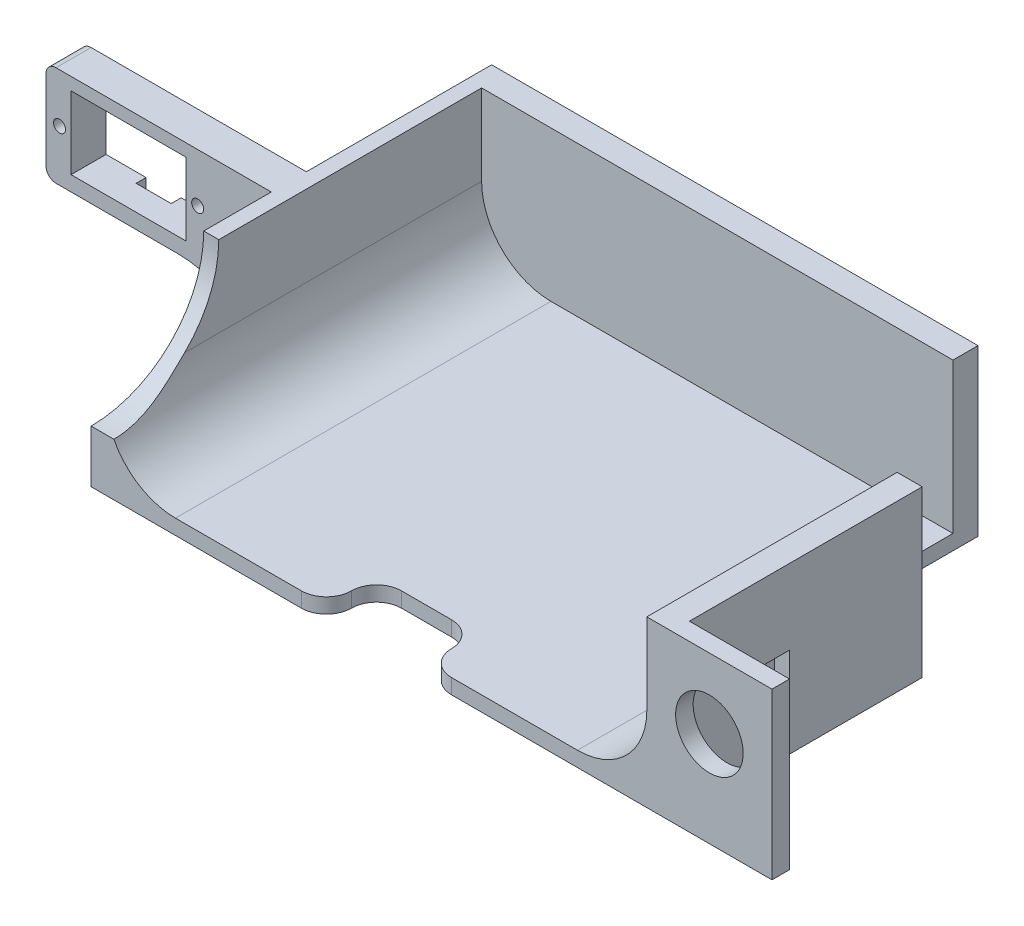
SolidWorks part; units mm, degrees
ref_plane "Plan de face" through (0, 0, 0) normal (0, 0, 1) x (1, 0, 0)
ref_plane "Plan de dessus" through (0, 0, 0) normal (0, 1, 0) x (1, 0, 0)
ref_plane "Plan de droite" through (0, 0, 0) normal (1, 0, 0) x (0, 0, -1)
sketch "Esquisse1" plane through (0, 0, 0) normal (0, 1, 0) x (1, 0, 0)
  line L1 (0, 0) -> (138, 0)
  line L2 (0, 0) -> (0, 75)
  line L3 (0, 75) -> (138, 75)
  line L4 (138, 0) -> (138, 75)
  dimension "D1" = 138
  dimension "D2" = 75
extrude "Boss.-Extru.1" add sketch "Esquisse1" along normal blind 3
sketch "Esquisse2" plane through (0, 3, 0) normal (0, 1, 0) x (1, 0, 0)
  line L0 (0, 0) -> (138, 0) construction
  line L1 (0, 75) -> (5, 75)
  line L2 (0, 75) -> (0, 0)
  line L3 (0, 0) -> (5, 0)
  line L4 (5, 75) -> (5, 0)
  line L6 (138, 75) -> (113, 75)
  line L7 (138, 75) -> (138, 0)
  line L8 (138, 0) -> (113, 0)
  line L9 (113, 75) -> (113, 0)
  dimension "D1" = 25
  dimension "D2" = 5
extrude "Boss.-Extru.2" add sketch "Esquisse2" along normal blind 30
fillet "Congé1" radius 13.85 2 edges at (113, 3, -37.5) (5, 3, -37.5)
sketch "Esquisse3" plane through (0, 0, -75) normal (0, 0, -1) x (-1, 0, 0)
  line L1 (-138, 0) -> (0, 0)
  line L2 (-138, 0) -> (-138, 33)
  line L3 (-138, 33) -> (0, 33)
  line L4 (0, 0) -> (0, 33)
extrude "Boss.-Extru.3" add sketch "Esquisse3" along normal blind 5
sketch "Esquisse4" plane through (0, 0, 0) normal (-1, 0, 0) x (0, 0, 1)
  line L1 (0, 33) -> (-25, 33)
  line L2 (0, 33) -> (0, 13)
  line L3 (0, 13) -> (-25, 13)
  line L4 (-25, 33) -> (-25, 13)
  dimension "D1" = 25
  dimension "D2" = 20
extrude "Enlèv. mat.-Extru.1" [suppressed] cut sketch "Esquisse4" against normal blind 6
sketch "Esquisse5" plane through (0, 33, 0) normal (0, 1, 0) x (1, 0, 0)
  line L0 (113, 75) -> (113, 0) construction
  line L1 (138, 80) -> (118, 80)
  line L2 (138, 80) -> (138, 3.5)
  line L3 (138, 3.5) -> (118, 3.5)
  line L4 (118, 80) -> (118, 3.5)
  line L5 (113, 0) -> (138, 0) construction
  dimension "D1" = 5
  dimension "D2" = 3.5
extrude "Enlèv. mat.-Extru.2" cut sketch "Esquisse5" against normal blind 30
sketch "Esquisse6" plane through (0, 0, 0) normal (0, 0, 1) x (1, 0, 0)
  line L0 (113, 33) -> (138, 33) construction
  line L3 (138, 33) -> (138, 0) construction
  circle A0 centre (125.5, 19) radius 6.25
  dimension "D3" = 12.5
  dimension "D1" = 14
  dimension "D2" = 12.5
extrude "Enlèv. mat.-Extru.3" cut sketch "Esquisse6" against normal up to surface (3.5 mm away) up to face at (128, 18, -3.5)
sketch "Esquisse7" plane through (0, 0, -80) normal (0, 0, -1) x (-1, 0, 0)
  line L1 (-138, 0) -> (-118, 0)
  line L2 (-138, 0) -> (-138, 3)
  line L3 (-138, 3) -> (-118, 3)
  line L4 (-118, 0) -> (-118, 3)
extrude "Enlèv. mat.-Extru.4" cut sketch "Esquisse7" against normal blind 30
sketch "Esquisse8" plane through (0, 33, 0) normal (0, 1, 0) x (1, 0, 0)
  line L0 (99.15, 0) -> (99.15, 75) construction
  line L1 (118, 80) -> (99.15, 80)
  line L2 (118, 80) -> (118, 50)
  line L3 (118, 50) -> (99.15, 50)
  line L4 (99.15, 80) -> (99.15, 50)
  dimension "D1" = 30
extrude "Enlèv. mat.-Extru.5" cut sketch "Esquisse8" against normal up to surface (33 mm away) up to face at (85.3333, 0, -43.3333)
sketch "Esquisse10" plane through (118, 0, 0) normal (1, 0, 0) x (0, 0, -1)
  line L0 (50, 3) -> (3.5, 3) construction
  line L1 (15.5, 3) -> (23.5, 3)
  line L2 (15.5, 3) -> (15.5, 18)
  line L3 (15.5, 18) -> (23.5, 18)
  line L4 (23.5, 3) -> (23.5, 18)
  dimension "D1" = 12
  dimension "D2" = 8
  dimension "D3" = 15
extrude "Enlèv. mat.-Extru.6" cut sketch "Esquisse10" against normal offset from surface (3 mm away) 2 up to face at (113, 24.925, -25)
sketch "Esquisse11" plane through (0, 3, 0) normal (0, 1, 0) x (1, 0, 0)
  line L1 (115, 23.5) -> (118, 23.5)
  line L2 (115, 23.5) -> (115, 15.5)
  line L3 (115, 15.5) -> (131, 15.5)
  line L8 (138, 3.5) -> (131, 3.5)
  line L9 (131, 15.5) -> (131, 3.5)
  line L10 (138, 50) -> (138, 3.5)
  line L11 (118, 50) -> (138, 50)
  line L12 (118, 50) -> (118, 23.5)
  dimension "D1" = 12
  dimension "D2" = 7
  dimension "D3" = 20
extrude "Enlèv. mat.-Extru.7" cut sketch "Esquisse11" against normal up to surface (3 mm away) up to face at (79.05, 0, -43.3333)
sketch "Esquisse12" plane through (0, 0, 0) normal (-1, 0, 0) x (0, 0, 1)
  line L1 (-80, 33) -> (0, 33)
  line L2 (-80, 33) -> (-80, 0)
  line L3 (-80, 0) -> (0, 0)
  line L4 (0, 33) -> (0, 0)
extrude "Enlèv. mat.-Extru.8" cut sketch "Esquisse12" against normal blind 2
sketch "Esquisse13" plane through (0, 0, 0) normal (0, 0, 1) x (1, 0, 0)
  line L0 (37, 0) -> (44.5969, -20)
  line L1 (2, 0) -> (138, 0) construction
  line L2 (44.5969, -20) -> (71.5969, -20)
  line L3 (71.5969, -20) -> (78, 0)
  line L4 (78, 0) -> (37, 0)
  line L7 (113, 33) -> (113, 16.85) construction
  dimension "D1" = 35
  dimension "D2" = 27
  dimension "D3" = 35
  dimension "D4" = 20
  dimension "D5" = 21
extrude "Boss.-Extru.4" [suppressed] add sketch "Esquisse13" against normal blind 7
sketch "Esquisse14" [suppressed] plane through (0, 0, 0) normal (0, 0, 1) x (1, 0, 0)
  line L0 (44.5969, -20) -> (71.5969, -20) construction
  line L1 (46.5, -2.5) -> (69.5, -2.5)
  line L2 (46.5, -2.5) -> (46.5, -17)
  line L3 (46.5, -17) -> (69.5, -17)
  line L4 (69.5, -2.5) -> (69.5, -17)
  dimension "D1" = 23
  dimension "D2" = 9.5
  dimension "D3" = 3
  dimension "D4" = 14.5
extrude "Enlèv. mat.-Extru.9" [suppressed] cut sketch "Esquisse14" against normal up to surface (7 mm away) up to face at (131.75, 19, 0)
fillet "Congé2" [suppressed] radius 10
sketch "Esquisse15" plane through (2, 0, 0) normal (-1, 0, 0) x (0, 0, 1)
  line L0 (0, 33) -> (-80, 33) construction
  line L1 (-42.9875, 33) -> (-35.9875, 33)
  line L2 (-42.9875, 33) -> (-42.9875, 13)
  line L3 (-42.9875, 13) -> (-35.9875, 13)
  line L4 (-35.9875, 33) -> (-35.9875, 13)
  dimension "D1" = 20
  dimension "D2" = 7
extrude "Boss.-Extru.5" add sketch "Esquisse15" along normal blind 45
sketch "Esquisse16" plane through (0, 0, -35.9875) normal (0, 0, 1) x (1, 0, 0)
  line L0 (-20.5, 33) -> (-20.5, 13) construction
  line L1 (-43, 33) -> (2, 33) construction
  line L2 (-43, 13) -> (2, 13) construction
  line L3 (-43, 23) -> (2, 23) construction
  line L4 (-43, 13) -> (-43, 33) construction
  line L5 (2, 13) -> (2, 33) construction
  line L7 (-38, 30.5) -> (-15, 30.5)
  line L8 (-38, 30.5) -> (-38, 16)
  line L9 (-38, 16) -> (-15, 16)
  line L10 (-15, 30.5) -> (-15, 16)
  dimension "D1" = 23
  dimension "D2" = 14.5
  dimension "D3" = 2.5
  dimension "D4" = 5
extrude "Enlèv. mat.-Extru.10" cut sketch "Esquisse16" against normal up to surface (7 mm away) up to face at (-20.5, 23, -42.9875)
fillet "Congé3" radius 20 1 edges at (2, 13, -39.4875)
fillet "Congé4" radius 2 2 edges at (-43, 33, -39.4875) (-43, 13, -39.4875)
sketch "Esquisse18" plane through (0, 0, -42.9875) normal (0, 0, -1) x (-1, 0, 0)
  line L0 (15, 16) -> (38, 16) construction
  line L1 (23, 16) -> (30, 16)
  line L2 (23, 16) -> (23, 13)
  line L3 (23, 13) -> (30, 13)
  line L4 (30, 16) -> (30, 13)
  line L6 (41, 13) -> (16.735, 13) construction
  dimension "D1" = 8
  dimension "D2" = 8
extrude "Enlèv. mat.-Extru.11" cut sketch "Esquisse18" against normal blind 2
sketch "Esquisse20" plane through (0, 0, -42.9875) normal (0, 0, -1) x (-1, 0, 0)
  line L0 (38, 30.5) -> (15, 30.5) construction
  line L1 (10.4, 25.9) -> (15, 25.9)
  line L2 (10.4, 25.9) -> (10.4, 20.6)
  line L3 (10.4, 20.6) -> (15, 20.6)
  line L4 (15, 25.9) -> (15, 20.6)
  line L5 (38, 25.9) -> (42.6, 25.9)
  line L6 (38, 25.9) -> (38, 20.6)
  line L7 (38, 20.6) -> (42.6, 20.6)
  line L8 (42.6, 25.9) -> (42.6, 20.6)
  line L9 (15, 16) -> (23, 16) construction
  line L10 (15, 30.5) -> (15, 16) construction
  line L11 (38, 16) -> (38, 30.5) construction
  line L12 (30, 16) -> (38, 16) construction
  dimension "D1" = 4.6
  dimension "D2" = 4.6
  dimension "D3" = 4.6
  dimension "D4" = 4.6
  dimension "D5" = 4.6
  dimension "D6" = 4.6
sketch "Esquisse21" plane through (0, 0, -42.9875) normal (0, 0, -1) x (-1, 0, 0)
  line L0 (15, 25.9) -> (15, 20.6) construction
  line L1 (10.4, 25.9) -> (10.4, 20.6) construction
  line L2 (10.4, 23.25) -> (15, 23.25) construction
  line L3 (15, 23.25) -> (42.6, 23.25) construction
  line L4 (42.6, 25.9) -> (42.6, 20.6) construction
  circle A0 centre (12.7, 23.25) radius 1
  circle A1 centre (40.3, 23.25) radius 1
  dimension "D1" = 2
  dimension "D3" = 2
  dimension "D2" = 2.3
extrude "Enlèv. mat.-Extru.12" cut sketch "Esquisse21" against normal up to surface (7 mm away) up to face at (-26.5, 23.25, -35.9875)
hole_wizard "Dégagement M21" positions "Esquisse22" profile "Esquisse23" hole size "M2" standard "ISO"
sketch "Esquisse22" plane through (0, 0, -42.9875) normal (0, 0, -1) x (-1, 0, 0)
  point P0 (40.3, 23.25)
  point P3 (12.7, 23.25)
sketch "Esquisse23" plane through (-40.3, 23.25, -42.9875) normal (1, 0, 0) x (0, 1, 0)
  line L0 (0, 0) -> (0, 10.721)
  line L1 (0, 10.721) -> (1.2, 10)
  line L2 (1.2, 10) -> (1.2, 0)
  line L5 (1.2, 0) -> (0, 0)
  line L10 (0, 10.721) -> (-1.2, 10) construction
  line L11 (0, -6.35) -> (0, 107.95) construction
  dimension "Diamètre du perçage" = 2.4
  dimension "Profondeur du perçage" = 10
  dimension "Angle de pointe" = 118
hole_wizard "Dégagement M121" positions "Esquisse24" profile "Esquisse25" hole size "M12" standard "ISO"
sketch "Esquisse24" plane through (0, 0, 0) normal (0, 0, 1) x (1, 0, 0)
  point P0 (125.5, 19)
sketch "Esquisse25" plane through (125.5, 19, 0) normal (1, 0, 0) x (0, -1, 0)
  line L0 (0, 0) -> (0, 14.0558)
  line L1 (0, 14.0558) -> (6.75, 10)
  line L2 (6.75, 10) -> (6.75, 0)
  line L5 (6.75, 0) -> (0, 0)
  line L10 (0, 14.0558) -> (-6.75, 10) construction
  line L11 (0, -6.35) -> (0, 107.95) construction
  dimension "Diamètre du perçage" = 13.5
  dimension "Profondeur du perçage" = 10
  dimension "Angle de pointe" = 118
sketch "Esquisse26" plane through (0, 0, 0) normal (0, 0, 1) x (1, 0, 0)
  line L0 (5, 33) -> (113, 33) construction
  line L1 (59, 33) -> (59, 0) construction
  line L2 (2, 0) -> (138, 0) construction
  line L3 (59, 3) -> (49, 3)
  line L4 (18.85, 3) -> (99.15, 3) construction
  line L5 (49, 3) -> (49, 0)
  line L6 (49, 0) -> (69, 0)
  line L7 (69, 0) -> (69, 3)
  line L8 (99.15, 3) -> (18.85, 3) construction
  line L9 (69, 3) -> (59, 3)
  dimension "D1" = 10
  dimension "D2" = 10
extrude "Enlèv. mat.-Extru.13" cut sketch "Esquisse26" against normal blind 10
fillet "Congé5" radius 5 4 edges at (69, 1.5, 0) (49, 1.5, 0) (49, 1.5, -10) (69, 1.5, -10)
sketch "Esquisse27" plane through (0, 0, 0) normal (0, -1, 0) x (1, 0, 0)
  line L0 (2, -80) -> (2, -42.9875) construction
  line L1 (2, -35.9875) -> (-8, -35.9875)
  line L2 (2, -35.9875) -> (2, -25.9875)
  line L3 (2, -25.9875) -> (-8, -25.9875)
  line L4 (-8, -35.9875) -> (-8, -25.9875)
  line L5 (2, -60) -> (-8, -60)
  line L6 (2, -60) -> (2, -70)
  line L7 (2, -70) -> (-8, -70)
  line L8 (-8, -60) -> (-8, -70)
  line L9 (99.15, -80) -> (2, -80) construction
  line L11 (12, -80) -> (22, -80)
  line L12 (12, -80) -> (12, -90)
  line L13 (12, -90) -> (22, -90)
  line L14 (22, -80) -> (22, -90)
  dimension "D1" = 10
  dimension "D2" = 10
  dimension "D3" = 10
  dimension "D4" = 10
  dimension "D5" = 10
  dimension "D6" = 10
  dimension "D7" = 10
  dimension "D8" = 10
extrude "Boss.-Extru.6" add sketch "Esquisse27" against normal blind 7
sketch "Esquisse28" plane through (0, 0, 0) normal (0, -1, 0) x (1, 0, 0)
  line L0 (118, -50) -> (99.15, -68.85)
  line L1 (99.15, -80) -> (99.15, -50) construction
  line L2 (99.15, -68.85) -> (99.15, -50)
  line L3 (99.15, -50) -> (118, -50)
  dimension "D1" = 18.85
extrude "Boss.-Extru.7" add sketch "Esquisse28" against normal blind 3
sketch "Esquisse31" plane through (0, 0, 0) normal (0, -1, 0) x (1, 0, 0)
  line L0 (2, -25.9875) -> (-8, -25.9875) construction
  line L1 (2, -25.9875) -> (2, 0) construction
  line L2 (2, -60) -> (-8, -60) construction
  line L6 (-8, -60) -> (-8, -70) construction
  line L7 (22, -90) -> (22, -80) construction
  line L8 (12, -90) -> (22, -90) construction
  line L9 (118, -50) -> (118, -23.5) construction
  circle A0 centre (-3, -30.9875) radius 1.5
  circle A1 centre (-3, -65) radius 1.5
  circle A2 centre (17, -85) radius 1.5
  circle A3 centre (104, -54.85) radius 1.5
  dimension "D3" = 3
  dimension "D6" = 3
  dimension "D8" = 3
  dimension "D11" = 3
  dimension "D1" = 5
  dimension "D2" = 5
  dimension "D4" = 5
  dimension "D5" = 5
  dimension "D7" = 5
  dimension "D9" = 5
  dimension "D10" = 14
  dimension "D12" = 14
extrude "Enlèv. mat.-Extru.14" cut sketch "Esquisse31" against normal blind 7
hole_wizard "Fraisage pour vis à tête fraisée M31" positions "Esquisse32" profile "Esquisse33" countersink size "M3" standard "ISO"
sketch "Esquisse32" plane through (0, 3, 0) normal (0, 1, 0) x (1, 0, 0)
  point P0 (104, 54.85)
sketch "Esquisse33" plane through (104, 3, -54.85) normal (1, 0, 0) x (0, 0, 1)
  line L0 (0, 0) -> (0, 11.0215)
  line L1 (0, 11.0215) -> (1.7, 10)
  line L2 (1.7, 10) -> (1.7, 1.45)
  line L3 (1.7, 1.45) -> (3.15, 0)
  line L5 (3.15, 0) -> (0, 0)
  line L6 (-1.7, 1.45) -> (-3.15, 0) construction
  line L10 (0, 11.0215) -> (-1.7, 10) construction
  line L11 (0, -6.35) -> (0, 107.95) construction
  dimension "Diamètre du perçage" = 3.4
  dimension "Profondeur du perçage" = 10
  dimension "Diamètre du fraisage entrant" = 6.3
  dimension "Angle du fraisage entrant" = 90
  dimension "Angle de pointe" = 118
hole_wizard "Fraisage pour vis à tête fraisée M32" positions "Esquisse34" profile "Esquisse35" countersink size "M3" standard "ISO"
sketch "Esquisse34" plane through (0, 7, 0) normal (0, 1, 0) x (1, 0, 0)
  point P0 (-3, 30.9875)
  point P3 (-3, 65)
  point P6 (17, 85)
sketch "Esquisse35" plane through (-3, 7, -30.9875) normal (1, 0, 0) x (0, 0, 1)
  line L0 (0, 0) -> (0, 11.0215)
  line L1 (0, 11.0215) -> (1.7, 10)
  line L2 (1.7, 10) -> (1.7, 1.45)
  line L3 (1.7, 1.45) -> (3.15, 0)
  line L5 (3.15, 0) -> (0, 0)
  line L6 (-1.7, 1.45) -> (-3.15, 0) construction
  line L10 (0, 11.0215) -> (-1.7, 10) construction
  line L11 (0, -6.35) -> (0, 107.95) construction
  dimension "Diamètre du perçage" = 3.4
  dimension "Profondeur du perçage" = 10
  dimension "Diamètre du fraisage entrant" = 6.3
  dimension "Angle du fraisage entrant" = 90
  dimension "Angle de pointe" = 118
sketch "Esquisse36" plane through (0, 3, 0) normal (0, 1, 0) x (1, 0, 0)
  line L1 (131, 15.5) -> (118, 15.5)
  line L2 (131, 15.5) -> (131, 3.5)
  line L3 (131, 3.5) -> (118, 3.5)
  line L4 (118, 15.5) -> (118, 3.5)
extrude "Enlèv. mat.-Extru.15" cut sketch "Esquisse36" against normal up to surface (3 mm away) up to face at (-3, 0, -32.6875)
sketch "Esquisse37" plane through (2, 0, 0) normal (-1, 0, 0) x (0, 0, 1)
  line L0 (0, 33) -> (0, 10.5)
  line L1 (0, 33) -> (-22.5, 33)
  arc A0 (-22.5, 33) -> (0, 10.5) centre (0, 33) ccw
  dimension "D1" = 45
extrude "Enlèv. mat.-Extru.16" cut sketch "Esquisse37" against normal blind 7
